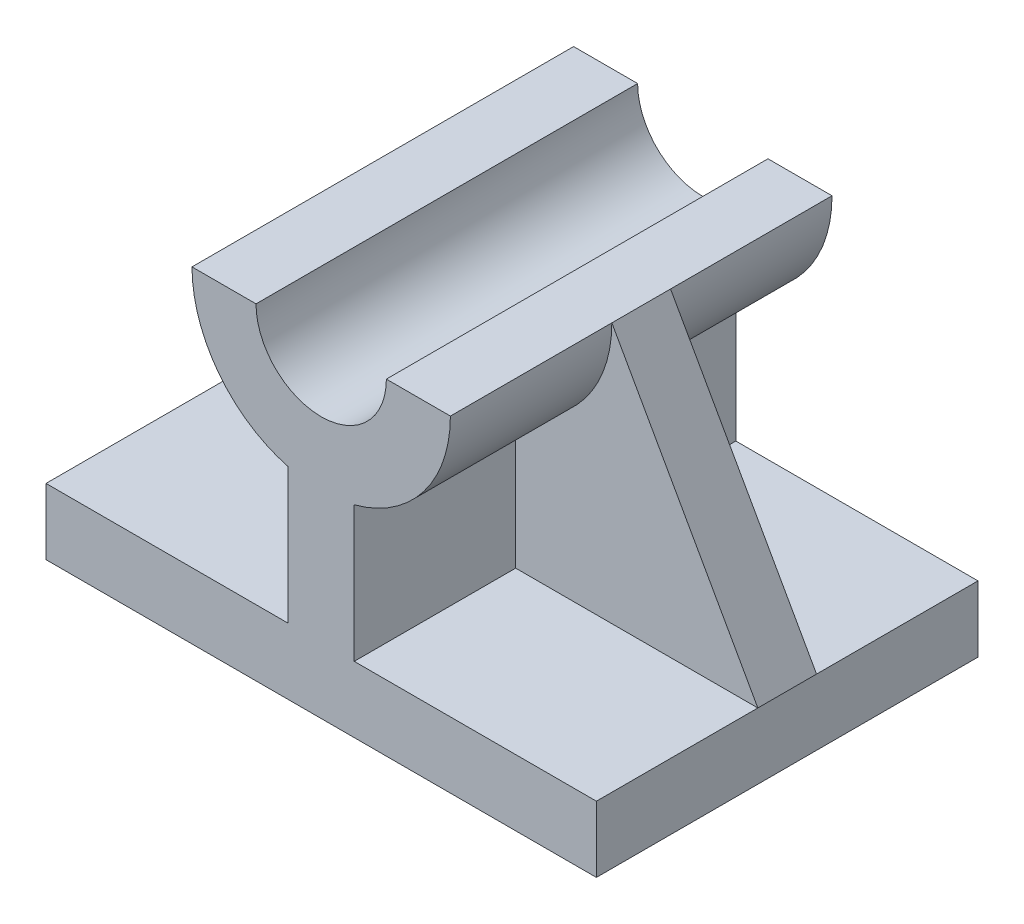
SolidWorks part; units mm, degrees
ref_plane "Front Plane" through (0, 0, 0) normal (0, 0, 1) x (1, 0, 0)
ref_plane "Top Plane" through (0, 0, 0) normal (0, 1, 0) x (1, 0, 0)
ref_plane "Right Plane" through (0, 0, 0) normal (1, 0, 0) x (0, 0, -1)
sketch "Sketch7" plane through (0, 0, 0) normal (0, 0, 1) x (1, 0, 0)
  line L0 (-17.6059, 40) -> (-8.8808, 40)
  line L1 (-37.5, 4.5) -> (-4.5, 4.5)
  line L2 (-37.5, 4.5) -> (-37.5, -4.5)
  line L3 (-37.5, -4.5) -> (37.5, -4.5)
  line L4 (37.5, 4.5) -> (37.5, -4.5)
  line L5 (-37.5, 4.5) -> (37.5, -4.5) construction
  line L6 (-37.5, -4.5) -> (37.5, 4.5) construction
  line L7 (4.5, 4.5) -> (37.5, 4.5)
  line L8 (-4.5, 22.9789) -> (-4.5, 4.5)
  line L9 (4.5, 22.9789) -> (4.5, 4.5)
  line L10 (8.8808, 40) -> (17.6059, 40)
  arc A0 (-8.8808, 40) -> (8.8808, 40) centre (0, 40) ccw
  arc A1 (-17.6059, 40) -> (-4.5, 22.9789) centre (0, 40) ccw
  arc A2 (4.5, 22.9789) -> (17.6059, 40) centre (0, 40) ccw
  point P0 (0, 0)
  dimension "D1" = 75
  dimension "D2" = 9
  dimension "D3" = 40
extrude "Boss-Extrude5" add sketch "Sketch7" along normal blind 26 and the other way blind 26
sketch "Sketch8" plane through (0, 0, 0) normal (0, 0, 1) x (1, 0, 0)
  line L0 (17.6059, 40) -> (37.5, 4.5)
  arc A0 (4.5, 22.9789) -> (17.6059, 40) centre (0, 40) ccw construction
rib "Rib1" sketch "Sketch8" sketch "Sketch8" thickness 8 extrusion direction parallel to sketch draft on no parameters "D1"=8
